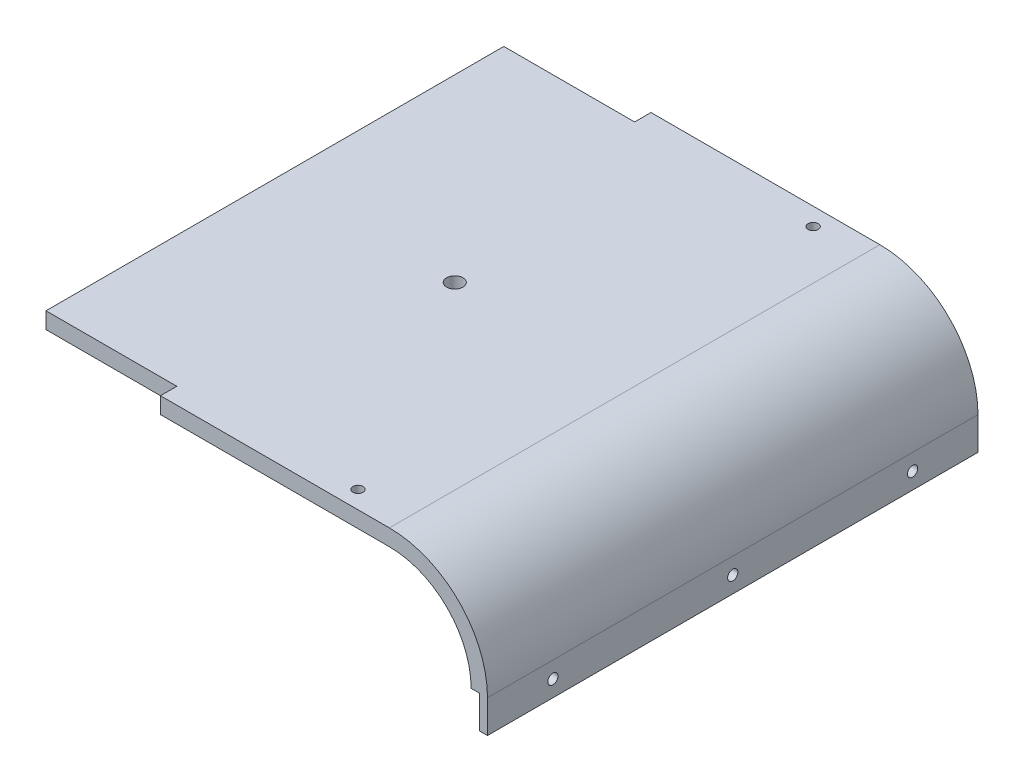
SolidWorks part; units mm, degrees
ref_plane "Front Plane" through (0, 0, 0) normal (0, 0, 1) x (1, 0, 0)
ref_plane "Top Plane" through (0, 0, 0) normal (0, 1, 0) x (1, 0, 0)
ref_plane "Right Plane" through (0, 0, 0) normal (1, 0, 0) x (0, 0, -1)
sketch "Sketch1" plane through (0, 0, 0) normal (0, 0, 1) x (1, 0, 0)
  line L0 (-139.7, 0) -> (139.7, 0)
  line L1 (139.7, 0) -> (139.7, -152.4) construction
  line L2 (139.7, -76.2) -> (215.9, -76.2) construction
  line L3 (-139.7, -12.7) -> (139.7, -12.7)
  line L4 (-139.7, 0) -> (-139.7, -12.7)
  line L5 (215.9, -76.2) -> (203.2, -76.2)
  circle A0 centre (139.7, -76.2) radius 76.2 construction
  arc A1 (139.7, 0) -> (215.9, -76.2) centre (139.7, -76.2) cw
  arc A2 (139.7, -12.7) -> (203.2, -76.2) centre (139.7, -76.2) cw
  point P4 (0, 0)
  dimension "D1" = 152.4
  dimension "D2" = 355.6
  dimension "D3" = 12.7
extrude "Boss-Extrude1" add sketch "Sketch1" along normal blind 190.5 and the other way blind 190.5
sketch "Sketch2" plane through (0, -76.2, 0) normal (0, -1, 0) x (1, 0, 0)
  line L0 (203.2, 190.5) -> (215.9, 190.5) construction
  line L1 (209.55, 190.5) -> (215.9, 190.5)
  line L2 (209.55, 190.5) -> (209.55, -190.5)
  line L3 (209.55, -190.5) -> (215.9, -190.5)
  line L4 (215.9, 190.5) -> (215.9, -190.5)
extrude "Boss-Extrude2" add sketch "Sketch2" along normal blind 25.4
sketch "Sketch3" plane through (215.9, 0, 0) normal (1, 0, 0) x (0, 0, -1)
  line L0 (-190.5, -88.9) -> (190.5, -88.9) construction
  line L1 (-190.5, -101.6) -> (-190.5, -76.2) construction
  line L2 (190.5, -101.6) -> (190.5, -76.2) construction
  line L3 (0, -76.2) -> (0, -101.6) construction
  line L4 (190.5, -76.2) -> (-190.5, -76.2) construction
  line L5 (190.5, -101.6) -> (-190.5, -101.6) construction
  line L6 (139.7, -76.2) -> (139.7, -101.6) construction
  line L7 (-139.7, -76.2) -> (-139.7, -101.6) construction
  circle A0 centre (-139.7, -88.9) radius 3.9687
  circle A1 centre (0, -88.9) radius 3.9687
  circle A2 centre (139.7, -88.9) radius 3.9687
  dimension "D3" = 7.9375
  dimension "D1" = 139.7
  dimension "D2" = 139.7
extrude "Cut-Extrude1" cut sketch "Sketch3" against normal blind 25.4
sketch "Sketch4" plane through (0, 0, 0) normal (0, 1, 0) x (1, 0, 0)
  circle A0 centre (0, 0) radius 6.35
  dimension "D1" = 12.7
extrude "Cut-Extrude2" cut sketch "Sketch4" against normal blind 17.78
sketch "Sketch5" plane through (0, 0, 0) normal (0, 1, 0) x (1, 0, 0)
  line L0 (139.7, 0) -> (101.6, 0) construction
  line L1 (139.7, 190.5) -> (139.7, -190.5) construction
  line L2 (-139.7, 190.5) -> (-139.7, -190.5) construction
  line L3 (0, 177.8) -> (0, -177.8) construction
  line L4 (101.6, 177.8) -> (101.6, -177.8) construction
  line L5 (-101.6, -177.8) -> (-101.6, 177.8) construction
  line L6 (139.7, -190.5) -> (-139.7, -190.5) construction
  line L7 (-101.6, 0) -> (-139.7, 0) construction
  line L8 (-101.6, 0) -> (0, 0) construction
  line L9 (0, 0) -> (101.6, 0) construction
  line L12 (-101.6, -177.8) -> (-139.7, -177.8)
  line L13 (-139.7, -177.8) -> (-139.7, -190.5)
  line L14 (-139.7, -190.5) -> (-38.1, -190.5)
  line L15 (-38.1, -190.5) -> (-38.1, -177.8)
  line L16 (-38.1, -177.8) -> (-101.6, -177.8)
  line L27 (-38.1, 190.5) -> (-38.1, 177.8)
  line L28 (-139.7, 190.5) -> (-38.1, 190.5)
  line L29 (-139.7, 177.8) -> (-139.7, 190.5)
  line L30 (-101.6, 177.8) -> (-139.7, 177.8)
  line L31 (-38.1, 177.8) -> (-101.6, 177.8)
  line L32 (139.7, 190.5) -> (-139.7, 190.5) construction
  circle A3 centre (101.6, -176.784) radius 3.937
  circle A4 centre (101.6, 176.784) radius 3.937
  point P11 (0, 0)
  point P15 (101.6, 0)
  point P18 (-101.6, 0)
  dimension "D3" = 13.716
  dimension "D2" = 7.874
  dimension "D1" = 12.7
  dimension "D4" = 101.6
  dimension "D5" = 13.716
  dimension "D6" = 101.6
extrude "Cut-Extrude3" cut sketch "Sketch5" against normal through all
